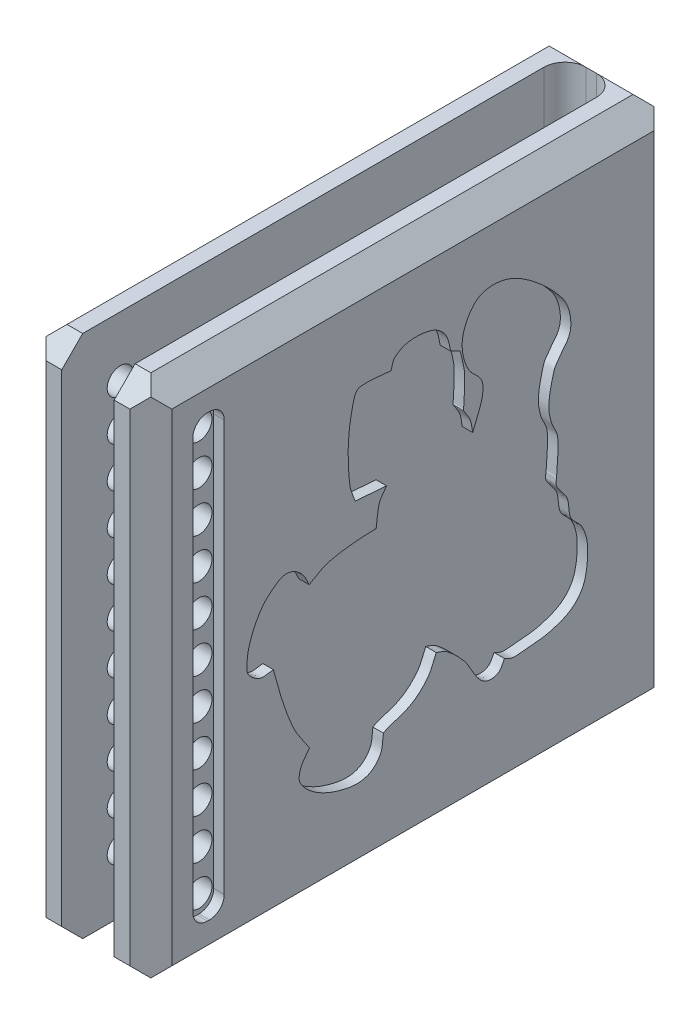
SolidWorks part; units mm, degrees
ref_plane "Front Plane" through (0, 0, 0) normal (0, 0, 1) x (1, 0, 0)
ref_plane "Top Plane" through (0, 0, 0) normal (0, 1, 0) x (1, 0, 0)
ref_plane "Right Plane" through (0, 0, 0) normal (1, 0, 0) x (0, 0, -1)
sketch "Sketch1" plane through (0, 0, 0) normal (0, 0, 1) x (1, 0, 0)
  line L1 (3, -12.5) -> (-3, -12.5)
  line L2 (3, -12.5) -> (3, 12.5)
  line L3 (3, 12.5) -> (-3, 12.5)
  line L4 (-3, -12.5) -> (-3, 12.5)
  line L5 (3, -12.5) -> (-3, 12.5) construction
  line L6 (3, 12.5) -> (-3, -12.5) construction
  point P0 (0, 0)
  dimension "D1" = 6
  dimension "D2" = 25
extrude "Boss-Extrude1" add sketch "Sketch1" along normal blind 25
sketch "Sketch2" plane through (0, 0, 25) normal (0, 0, 1) x (1, 0, 0)
  line L0 (3, 12.5) -> (-3, 12.5) construction
  line L1 (1.25, -12.5) -> (-1.25, -12.5)
  line L2 (1.25, -12.5) -> (1.25, 12.5)
  line L3 (1.25, 12.5) -> (-1.25, 12.5)
  line L4 (-1.25, -12.5) -> (-1.25, 12.5)
  line L5 (1.25, -12.5) -> (-1.25, 12.5) construction
  line L6 (1.25, 12.5) -> (-1.25, -12.5) construction
  point P0 (0, 0)
  dimension "D1" = 2.5
extrude "Cut-Extrude1" cut sketch "Sketch2" against normal blind 24
fillet "Fillet2" radius 1 2 edges at (1.25, 0, 1) (-1.25, 0, 1)
chamfer "Chamfer1" distance 1 angle 45 4 edges at (-3, 12.5, 12.5) (-3, -12.5, 12.5) (-3, 0, 25) (3, 0, 25)
chamfer "Chamfer2" distance 1 angle 45 4 edges at (-3, 0, 0) (3, -12.5, 12) (3, 12.5, 12) (3, 0, 0)
chamfer "Chamfer3" distance 1 angle 45 2 edges at (0, -12.5, 0) (0, 12.5, 0)
chamfer "Chamfer4" distance 1 angle 45 4 edges at (-1.625, 12.5, 25) (1.625, 12.5, 25) (1.625, -12.5, 25) (-1.625, -12.5, 25)
sketch "Sketch3" plane through (-3, 0, 0) normal (-1, 0, 0) x (0, 0, 1)
  line L0 (24, -11.5) -> (24, 11.5) construction
  line L1 (22.3, 10.5) -> (22.2, 10.5)
  line L2 (23, 9.8) -> (23, -9.8)
  line L3 (22.3, -10.5) -> (22.2, -10.5)
  line L4 (21.5, 9.8) -> (21.5, -9.8)
  line L5 (24, 11.5) -> (1, 11.5) construction
  line L6 (1, -11.5) -> (24, -11.5) construction
  arc A0 (21.5, -9.8) -> (22.2, -10.5) centre (22.2, -9.8) ccw
  arc A1 (22.3, -10.5) -> (23, -9.8) centre (22.3, -9.8) ccw
  arc A2 (23, 9.8) -> (22.3, 10.5) centre (22.3, 9.8) ccw
  arc A3 (22.2, 10.5) -> (21.5, 9.8) centre (22.2, 9.8) ccw
  point P14 (23, -10.5)
  point P17 (23, 10.5)
  point P20 (21.5, 10.5)
  dimension "D6" = 0.7
  dimension "D1" = 1.5
  dimension "D2" = 1
  dimension "D3" = 1
  dimension "D4" = 1
  dimension "D5" = 21
extrude "Cut-Extrude2" cut sketch "Sketch3" against normal blind 0.5
sketch "Sketch4" plane through (-2.5, 0, 0) normal (-1, 0, 0) x (0, 0, 1)
  line L0 (23, -9.8) -> (23, 9.8) construction
  circle A0 centre (22.2066, 0) radius 0.625
  dimension "D1" = 1.25
  dimension "D2" = 0.7934
extrude "Cut-Extrude3" cut sketch "Sketch4" against normal up to next
pattern_linear "LPattern1" count 6 spacing 1.93 along (0, -1, 0) count 6 spacing 1.93 along (0, 1, 0) of "Cut-Extrude3"
mirror "Mirror1" about plane through (0, 0, 0) normal (1, 0, 0) of "LPattern1", "Cut-Extrude3", "Cut-Extrude2"
sketch "Sketch6" plane through (0, 0, 0) normal (1, 0, 0) x (0, 0, -1)
  line L0 (-13.7566, 3.2081) -> (-15.2566, 3.3281)
  line L1 (-10.6966, 7.2431) -> (-10.2466, 7.0331)
  spline S0 degree 3 poles (-19.1566, -1.6819) (-19.3616, -1.6969) (-19.5715, -1.7741) (-19.7716, -1.7269) (-19.9511, -1.6845) (-20.1062, -1.5573) (-20.2366, -1.4269) (-20.3283, -1.3352) (-20.4124, -1.2115) (-20.4166, -1.0819) (-20.428, -0.7292) (-20.3898, -0.3678) (-20.2816, -0.0319) (-20.1465, 0.3874) (-19.9535, 0.7952) (-19.6966, 1.1531) (-19.5005, 1.4263) (-19.2243, 1.6383) (-18.9466, 1.8281) (-18.8213, 1.9138) (-18.6632, 1.9704) (-18.5116, 1.9631) (-18.3362, 1.9546) (-18.1565, 1.8892) (-18.0166, 1.7831) (-17.6811, 1.5287) (-17.6019, 1.3009) (-17.4466, 0.9731) knots 0 0 0 0 1 1 1 2 2 2 3 3 3 4 4 4 5 5 5 6 6 6 7 7 7 8 8 8 9 9 9 9
  spline S1 degree 3 poles (-17.4466, 0.9731) (-17.1416, 1.1281) (-16.8621, 1.3498) (-16.5316, 1.4381) (-15.7927, 1.6354) (-15.0161, 1.6724) (-14.2516, 1.6931) knots 0 0 0 0 1 1 1 2 2 2 2
  spline S2 degree 3 poles (-14.2516, 1.6931) (-14.2016, 2.0181) (-14.2037, 2.3555) (-14.1016, 2.6681) (-14.0353, 2.8711) (-13.8716, 3.0281) (-13.7566, 3.2081) knots 0 0 0 0 1 1 1 2 2 2 2
  spline S3 degree 3 poles (-15.2566, 3.3281) (-15.3416, 3.5981) (-15.4781, 3.857) (-15.5116, 4.1381) (-15.5839, 4.7441) (-15.6106, 5.359) (-15.5716, 5.9681) (-15.5353, 6.5349) (-15.4448, 7.1026) (-15.2866, 7.6481) (-15.2492, 7.7771) (-15.135, 7.917) (-15.0016, 7.9331) (-14.5195, 7.9913) (-14.0316, 7.8831) (-13.5466, 7.8581) knots 0 0 0 0 1 1 1 2 2 2 3 3 3 4 4 4 5 5 5 5
  spline S4 degree 3 poles (-13.5466, 7.8581) (-13.4816, 8.0131) (-13.4767, 8.2109) (-13.3516, 8.3231) (-13.1667, 8.4888) (-12.9225, 8.6036) (-12.6766, 8.6381) (-12.334, 8.6862) (-11.9743, 8.6577) (-11.6416, 8.5631) (-11.4122, 8.4978) (-11.1979, 8.3533) (-11.0416, 8.1731) (-10.8045, 7.8998) (-10.762, 7.5702) (-10.6966, 7.2431) knots 0 0 0 0 1 1 1 2 2 2 3 3 3 4 4 4 5 5 5 5
  spline S5 degree 3 poles (-10.2466, 7.0331) (-10.1766, 6.6931) (-10.0595, 6.3595) (-10.0366, 6.0131) (-10.0042, 5.5239) (-10.0622, 5.0329) (-10.0816, 4.5431) (-10.0822, 4.5273) (-10.1039, 4.5121) (-10.0966, 4.4981) (-9.9965, 4.3075) (-9.8456, 4.1433) (-9.7666, 3.9431) (-9.6935, 3.7579) (-9.6866, 3.5531) (-9.6466, 3.3581) knots 0 0 0 0 1 1 1 2 2 2 3 3 3 4 4 4 5 5 5 5
  spline S6 degree 3 poles (-9.6466, 3.3581) (-9.4966, 3.7681) (-9.2885, 4.1613) (-9.1966, 4.5881) (-9.146, 4.8229) (-9.129, 5.0886) (-9.2266, 5.3081) (-9.3608, 5.61) (-9.7007, 5.7818) (-9.8566, 6.0731) (-10.0118, 6.3632) (-10.1086, 6.6907) (-10.1416, 7.0181) (-10.1699, 7.2988) (-10.139, 7.5951) (-10.0366, 7.8581) (-9.9133, 8.1747) (-9.7429, 8.4959) (-9.4816, 8.7131) (-9.2713, 8.888) (-8.975, 8.9611) (-8.7016, 8.9681) (-8.3644, 8.9767) (-8.0173, 8.9006) (-7.7116, 8.7581) (-7.2641, 8.5495) (-6.8571, 8.2536) (-6.4816, 7.9331) (-6.0673, 7.5795) (-5.6797, 7.1866) (-5.3566, 6.7481) (-5.1825, 6.5118) (-5.0697, 6.2258) (-5.0116, 5.9381) (-4.9572, 5.6685) (-4.9381, 5.3735) (-5.0266, 5.1131) (-5.1261, 4.8202) (-5.3824, 4.607) (-5.5516, 4.3481) (-5.6276, 4.2318) (-5.7233, 4.1216) (-5.7616, 3.9881) (-5.8798, 3.5762) (-5.9852, 3.1555) (-6.0166, 2.7281) (-6.0358, 2.4665) (-5.9792, 2.2016) (-5.9116, 1.9481) (-5.8382, 1.6727) (-5.6285, 1.4364) (-5.5966, 1.1531) (-5.5368, 0.6212) (-5.6223, 0.083) (-5.6416, -0.4519) (-5.6423, -0.4725) (-5.6566, -0.4913) (-5.6566, -0.5119) (-5.6566, -0.632) (-5.6923, -0.763) (-5.6416, -0.8719) (-5.5169, -1.1397) (-5.2593, -1.3339) (-5.1466, -1.6069) (-5.0298, -1.8897) (-5.0958, -2.2296) (-4.9666, -2.5069) (-4.8482, -2.7611) (-4.5559, -2.9031) (-4.4266, -3.1519) (-4.285, -3.4243) (-4.1929, -3.7306) (-4.1716, -4.0369) (-4.1421, -4.4623) (-4.1746, -4.8978) (-4.2766, -5.3119) (-4.3429, -5.5812) (-4.4795, -5.8421) (-4.6666, -6.0469) (-4.8611, -6.2599) (-5.1189, -6.4194) (-5.3866, -6.5269) (-5.7636, -6.6783) (-6.1667, -6.7784) (-6.5716, -6.8119) (-7.79, -6.9129) (-7.6522, -6.9766) (-8.1316, -6.7369) knots 0 0 0 0 1 1 1 2 2 2 3 3 3 4 4 4 5 5 5 6 6 6 7 7 7 8 8 8 9 9 9 10 10 10 11 11 11 12 12 12 13 13 13 14 14 14 15 15 15 16 16 16 17 17 17 18 18 18 19 19 19 20 20 20 21 21 21 22 22 22 23 23 23 24 24 24 25 25 25 26 26 26 27 27 27 28 28 28 29 29 29 29
  spline S7 degree 3 poles (-8.1316, -6.7369) (-8.2216, -6.8769) (-8.2644, -7.0627) (-8.4016, -7.1569) (-8.5407, -7.2523) (-8.7309, -7.2935) (-8.8966, -7.2619) (-9.071, -7.2287) (-9.2326, -7.1131) (-9.3466, -6.9769) (-9.6252, -6.644) (-9.7782, -6.2191) (-10.0516, -5.8819) (-10.2966, -5.5798) (-10.5825, -5.3081) (-10.8916, -5.0719) (-11.034, -4.9631) (-11.2216, -4.9319) (-11.3866, -4.8619) knots 0 0 0 0 1 1 1 2 2 2 3 3 3 4 4 4 5 5 5 6 6 6 6
  spline S8 degree 3 poles (-11.3866, -4.8619) (-11.5166, -5.1319) (-11.5949, -5.4336) (-11.7766, -5.6719) (-11.9868, -5.9477) (-12.2436, -6.1995) (-12.5416, -6.3769) (-12.9102, -6.5964) (-13.3442, -6.6803) (-13.7416, -6.8419) (-13.7996, -6.8655) (-13.8516, -6.9019) (-13.9066, -6.9319) knots 0 0 0 0 1 1 1 2 2 2 3 3 3 4 4 4 4
  spline S9 degree 3 poles (-13.9066, -6.9319) (-13.9566, -7.2019) (-13.9264, -7.5001) (-14.0566, -7.7419) (-14.184, -7.9786) (-14.3925, -8.1958) (-14.6416, -8.2969) (-14.9294, -8.4137) (-15.2665, -8.4152) (-15.5716, -8.3569) (-16.0671, -8.2622) (-16.5605, -8.1006) (-16.9966, -7.8469) (-17.3421, -7.646) (-17.6626, -7.3656) (-17.8666, -7.0219) (-17.9713, -6.8456) (-17.9192, -6.6005) (-17.8516, -6.4069) (-17.7683, -6.1686) (-17.5716, -5.9869) (-17.4316, -5.7769) knots 0 0 0 0 1 1 1 2 2 2 3 3 3 4 4 4 5 5 5 6 6 6 7 7 7 7
  spline S10 degree 3 poles (-17.4316, -5.7769) (-17.6866, -5.3769) (-17.9967, -5.0071) (-18.1966, -4.5769) (-18.6251, -3.655) (-18.8946, -2.6643) (-19.1566, -1.6819) knots 0 0 0 0 1 1 1 2 2 2 2
extrude "Cut-Extrude4" cut sketch "Sketch6" against normal blind 0.5 from surface at 3 starting at face at (3, 0, 12.5)
sketch "Sketch7" plane through (-3, 0, 0) normal (-1, 0, 0) x (0, 0, 1)
  line L0 (24, 11.5) -> (1, 11.5) construction
  line L1 (5, 7.5) -> (6, 7.5)
  line L2 (5, 7.5) -> (5, -7.5)
  line L3 (5, -7.5) -> (6, -7.5)
  line L4 (6, 7.5) -> (6, -7.5)
  line L5 (1, -11.5) -> (24, -11.5) construction
  line L6 (1, 11.5) -> (1, -11.5) construction
  dimension "D1" = 1
  dimension "D2" = 4
  dimension "D3" = 4
  dimension "D4" = 4
extrude "Cut-Extrude5" cut sketch "Sketch7" against normal blind 0.5
pattern_linear "LPattern2" count 7 spacing 2 along (0, 0, 1) of "Cut-Extrude5"
